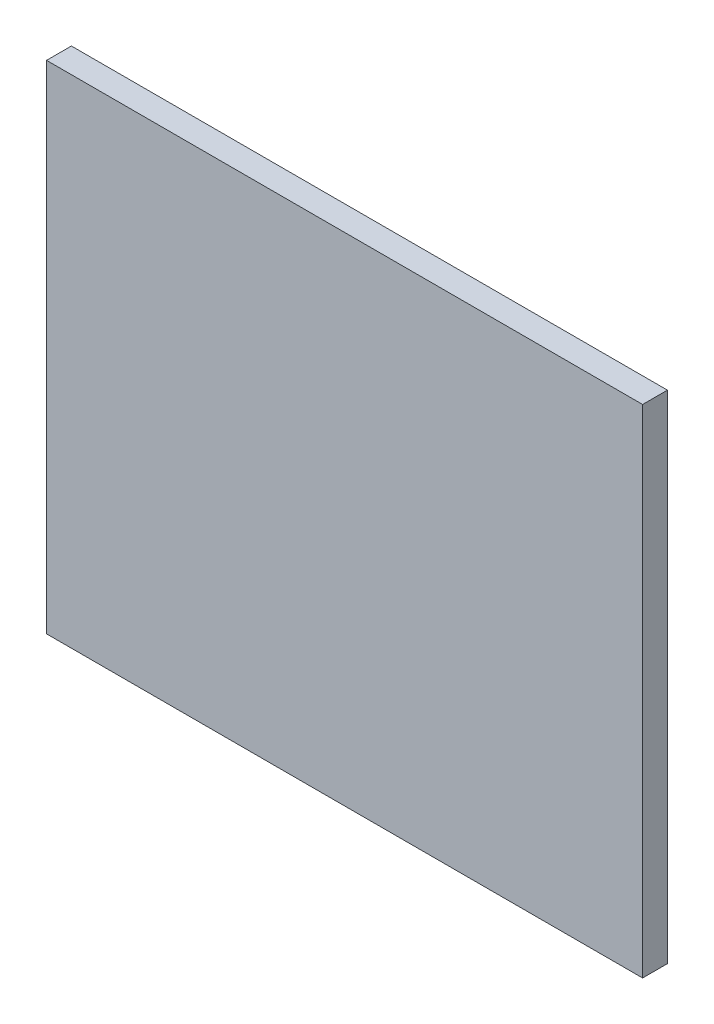
SolidWorks part; units mm, degrees
ref_plane "Plan de face" through (0, 0, 0) normal (0, 0, 1) x (1, 0, 0)
ref_plane "Plan de dessus" through (0, 0, 0) normal (0, 1, 0) x (1, 0, 0)
ref_plane "Plan de droite" through (0, 0, 0) normal (1, 0, 0) x (0, 0, -1)
sketch "Esquisse1" plane through (0, 0, 0) normal (0, 0, 1) x (1, 0, 0)
  line L0 (-14.15, 14.15) -> (-14.15, -14.15)
  line L1 (-10.15, 10.15) -> (10.15, 10.15)
  line L2 (-10.15, 10.15) -> (-10.15, -10.15)
  line L3 (-10.15, -10.15) -> (10.15, -10.15)
  line L4 (10.15, 10.15) -> (10.15, -10.15)
  line L5 (-10.15, 10.15) -> (10.15, -10.15) construction
  line L6 (-10.15, -10.15) -> (10.15, 10.15) construction
  line L7 (-14.15, -14.15) -> (14.15, -14.15)
  line L8 (14.15, 14.15) -> (14.15, -14.15)
  line L9 (-14.15, 14.15) -> (14.15, 14.15)
  line L10 (10.15, 0) -> (14.15, 0)
  line L11 (14.15, 0) -> (14.15, -2)
  line L12 (14.15, -2) -> (10.15, -2)
  line L13 (10.15, -2) -> (10.15, 0)
  line L14 (14.15, 0) -> (14.15, -2)
  line L15 (10.15, 0) -> (10.15, -2)
  point P0 (0, 0)
  dimension "D1" = 20.3
  dimension "D2" = 4
  dimension "D3" = 2
extrude "Boss.-Extru.1" add sketch "Esquisse1" along normal blind 20 contours L8 L12 L4 L3 L2 L1 L10 L9 L0 L7 | L13 L10 L11 L12 region at (0, 13.7498, 0)
extrude "Boss.-Extru.7" add sketch "Esquisse1<3>" against normal blind 20 contours L8 L12 L4 L3 L2 L1 L10 L9 L0 L7 region at (0, 13.7498, 0)
sketch "Esquisse1<3>" plane through (0, 0, 0) normal (0, 0, 1) x (1, 0, 0) same geometry as "Esquisse1"
ref_plane "Plan1" through (0, 2, 0) normal (0, -1, 0) x (-1, 0, 0)
sketch "Esquisse2" plane through (0, 2, 0) normal (0, -1, 0) x (-1, 0, 0)
  line L0 (-22.65, 0) -> (-14.15, 0) construction
  line L1 (-14.15, 20) -> (-22.65, 20)
  line L2 (-14.15, 20) -> (-14.15, -20)
  line L3 (-14.15, -20) -> (-22.65, -20) construction
  line L4 (-22.65, 20) -> (-22.65, -20)
  line L5 (-15.65, 8.4123) -> (-15.65, 11.5877)
  line L6 (-15.65, 11.5877) -> (-18.4, 13.1754)
  line L7 (-18.4, 13.1754) -> (-21.15, 11.5877)
  line L8 (-21.15, 11.5877) -> (-21.15, 8.4123)
  line L9 (-21.15, 8.4123) -> (-18.4, 6.8246)
  line L10 (-18.4, 6.8246) -> (-15.65, 8.4123)
  line L11 (-18.4, -6.8246) -> (-15.65, -8.4123) construction
  line L12 (-21.15, -8.4123) -> (-18.4, -6.8246) construction
  line L13 (-21.15, -11.5877) -> (-21.15, -8.4123) construction
  line L14 (-18.4, -13.1754) -> (-21.15, -11.5877) construction
  line L15 (-15.65, -11.5877) -> (-18.4, -13.1754) construction
  line L16 (-15.65, -8.4123) -> (-15.65, -11.5877) construction
  line L17 (-22.65, 0) -> (-14.15, -20) construction
  line L18 (-22.65, 0) -> (-14.15, 0)
  circle A0 centre (-18.4, 10) radius 2.75 construction
  circle A1 centre (-18.4, 10) radius 1.7
  circle A2 centre (-18.4, -10) radius 1.7 construction
  point P23 (-18.4, -10)
  dimension "D1" = 3.4
  dimension "D2" = 5.5
  dimension "D3" = 1.5
extrude "Boss.-Extru.2" add sketch "Esquisse2" along normal up to vertex (2 mm away) contours L1 L4 L3 L2 L10 L9 L8 L7 L6 L5 L11 L16 L15 L14 L13 L12 | L9 L10 L5 L6 L7 L8 A1 | L16 L11 L12 L13 L14 L15 A2 region at (14.3673, 2, -10) region at (17.067, 2, -7.6912) up to point (14.15, 0, -20)
extrude "Boss.-Extru.3" add sketch "Esquisse2<3>" against normal blind 3 contours L1 L4 L3 L2 L10 L9 L8 L7 L6 L5 L11 L16 L15 L14 L13 L12 region at (14.3673, 2, -10)
sketch "Esquisse2<3>" plane through (0, 2, 0) normal (0, -1, 0) x (-1, 0, 0) same geometry as "Esquisse2"
sketch "Esquisse3" plane through (0, -2, 0) normal (0, 1, 0) x (1, 0, 0)
  line L4 (22.65, 20) -> (14.15, 20)
  line L5 (14.15, 20) -> (14.15, 0)
  line L6 (14.15, 0) -> (22.65, 0)
  line L7 (22.65, 0) -> (22.65, 20)
  line L8 (22.65, 20) -> (14.15, 20)
  line L9 (14.15, 20) -> (14.15, 0)
  line L11 (22.65, 0) -> (22.65, 20)
  line L12 (14.15, 0) -> (22.65, 0)
  circle A0 centre (18.4, 10) radius 1.7 construction
  circle A1 centre (18.4, 10) radius 1.7
  dimension "D1" = 0
extrude "Boss.-Extru.4" add sketch "Esquisse3" against normal blind 2
sketch "Esquisse5" plane through (0, -4, 0) normal (0, -1, 0) x (1, 0, 0)
  line L0 (22.65, 0) -> (22.65, -20)
  line L3 (14.15, 0) -> (22.65, 0)
  line L5 (22.65, -20) -> (14.15, -20)
  line L6 (22.65, -20) -> (14.15, -20) construction
  line L7 (14.15, -20) -> (14.15, 0)
  line L8 (14.15, -20) -> (14.15, 0) construction
  circle A1 centre (18.4, -10) radius 3
  dimension "D1" = 6
extrude "Boss.-Extru.5" add sketch "Esquisse5" along normal blind 2
ref_plane "Plan3" through (0, 0, 0) normal (0, -1, 0) x (-1, 0, 0)
sketch "Esquisse6" plane through (0, 0, 0) normal (0, -1, 0) x (-1, 0, 0)
  line L0 (-14.15, -20) -> (14.15, -48.3) construction
  line L1 (14.15, -20) -> (-14.15, -20)
  line L2 (14.15, -20) -> (14.15, -48.3)
  line L3 (14.15, -48.3) -> (-14.15, -48.3)
  line L4 (-14.15, -20) -> (-14.15, -48.3)
  line L6 (-7.65, -26.5) -> (7.65, -26.5)
  line L7 (-7.65, -26.5) -> (-7.65, -41.8)
  line L8 (-7.65, -41.8) -> (7.65, -41.8)
  line L9 (7.65, -26.5) -> (7.65, -41.8)
  line L10 (-7.65, -26.5) -> (7.65, -41.8) construction
  line L11 (-7.65, -41.8) -> (7.65, -26.5) construction
  point P5 (0, -34.15)
  dimension "D1" = 15.3
extrude "Boss.-Extru.6" add sketch "Esquisse6" along normal blind 20 and the other way blind 20
sketch "Esquisse7" plane through (0, -20, 0) normal (0, -1, 0) x (1, 0, 0)
  line L0 (7.65, 34.15) -> (14.15, 34.15) construction
  line L1 (7.65, 26.5) -> (7.65, 41.8) construction
  line L2 (14.15, 20) -> (14.15, 48.3) construction
  line L3 (7.65, 34.15) -> (14.15, 34.15)
  line L4 (14.15, 34.15) -> (14.15, 36.15)
  line L5 (14.15, 36.15) -> (7.65, 36.15)
  line L6 (7.65, 36.15) -> (7.65, 34.15)
  dimension "D1" = 2
extrude "Enlèv. mat.-Extru.1" cut sketch "Esquisse7" against normal up to next
sketch "Esquisse8" plane through (0, -14.15, 0) normal (0, -1, 0) x (1, 0, 0)
  line L0 (14.15, 20) -> (14.15, -20) construction
  line L1 (14.15, 0) -> (0, 0)
  line L2 (14.15, 0) -> (14.15, 2)
  line L3 (14.15, 2) -> (0, 2)
  line L4 (0, 0) -> (0, 2)
  dimension "D1" = 2
extrude "Enlèv. mat.-Extru.2" cut sketch "Esquisse8" against normal up to next
sketch "Esquisse9" plane through (0, 0, 34.15) normal (0, 0, 1) x (1, 0, 0)
  line L0 (14.15, 20) -> (14.15, -20) construction
  line L1 (14.15, 20) -> (22.65, 20)
  line L2 (14.15, 20) -> (14.15, -20)
  line L3 (14.15, -20) -> (22.65, -20)
  line L4 (22.65, 20) -> (22.65, -20)
  line L5 (7.65, 20) -> (14.15, 20) construction
  line L6 (18.4, 20) -> (18.4, -20) construction
  line L7 (21.15, 8.4123) -> (21.15, 11.5877)
  line L8 (21.15, 11.5877) -> (18.4, 13.1754)
  line L9 (18.4, 13.1754) -> (15.65, 11.5877)
  line L10 (15.65, 11.5877) -> (15.65, 8.4123)
  line L11 (15.65, 8.4123) -> (18.4, 6.8246)
  line L12 (18.4, 6.8246) -> (21.15, 8.4123)
  line L13 (22.65, 0) -> (14.15, 0) construction
  line L14 (22.65, 20) -> (14.15, 0) construction
  line L15 (18.4, -6.8246) -> (21.15, -8.4123)
  line L16 (15.65, -8.4123) -> (18.4, -6.8246)
  line L17 (15.65, -11.5877) -> (15.65, -8.4123)
  line L18 (18.4, -13.1754) -> (15.65, -11.5877)
  line L19 (21.15, -11.5877) -> (18.4, -13.1754)
  line L20 (21.15, -8.4123) -> (21.15, -11.5877)
  circle A0 centre (18.4, 10) radius 2.75 construction
  circle A1 centre (18.4, 10) radius 1.7
  circle A2 centre (18.4, -10) radius 1.7
  line M16 (14.15, -20) -> (14.15, 20)
  dimension "D2" = 3.4
  dimension "D1" = 5.5
  dimension "D3" = 1.5
extrude "Boss.-Extru.8" add sketch "Esquisse9" against normal blind 5 contours L4 L1 L3 L12 L11 L10 L9 L8 L7 L15 L20 L19 L18 L17 L16 M16 region at (18.4, 0, 34.15)
extrude "Boss.-Extru.9" add sketch "Esquisse9<4>" against normal blind 2 contours L11 L12 L7 L8 L9 L10 A1 | L20 L15 L16 L17 L18 L19 A2 region at (19.733, 7.6912, 34.15) region at (19.733, -7.6912, 34.15)
sketch "Esquisse9<4>" plane through (0, 0, 34.15) normal (0, 0, 1) x (1, 0, 0) same geometry as "Esquisse9"
sketch "Esquisse10" plane through (0, 0, 36.15) normal (0, 0, -1) x (-1, 0, 0)
  line L4 (-22.65, 20) -> (-22.65, -20)
  line L5 (-22.65, -20) -> (-14.15, -20)
  line L6 (-14.15, -20) -> (-14.15, 20)
  line L7 (-14.15, 20) -> (-22.65, 20)
  line L8 (-22.65, 20) -> (-22.65, -20)
  line L9 (-22.65, -20) -> (-14.15, -20)
  line L10 (-14.15, -20) -> (-14.15, 20)
  line L11 (-14.15, 20) -> (-22.65, 20)
  circle A0 centre (-18.4, -10) radius 1.7 construction
  circle A1 centre (-18.4, 10) radius 1.7 construction
  circle A2 centre (-18.4, -10) radius 1.7
  circle A3 centre (-18.4, 10) radius 1.7
  dimension "D1" = 0
extrude "Boss.-Extru.10" add sketch "Esquisse10" against normal blind 2
sketch "Esquisse11" plane through (0, 0, 38.15) normal (0, 0, 1) x (1, 0, 0)
  line L4 (22.65, 20) -> (14.15, 20)
  line L5 (14.15, 20) -> (14.15, -20)
  line L6 (14.15, -20) -> (22.65, -20)
  line L7 (22.65, -20) -> (22.65, 20)
  line L8 (22.65, 20) -> (14.15, 20)
  line L9 (14.15, 20) -> (14.15, -20)
  line L10 (14.15, -20) -> (22.65, -20)
  line L11 (22.65, -20) -> (22.65, 20)
  circle A0 centre (18.4, 10) radius 3
  circle A1 centre (18.4, -10) radius 3
  dimension "D1" = 6
  dimension "D2" = 0
extrude "Boss.-Extru.11" add sketch "Esquisse11" along normal blind 2
sketch "Esquisse14" plane through (0, -20, 0) normal (0, -1, 0) x (1, 0, 0)
  line L0 (14.15, 48.3) -> (22.65, 40.15)
rib "Nervure4" sketch "Esquisse14" sketch "Esquisse14" thickness 5 extrusion direction parallel to sketch draft on no parameters "D1"=5
ref_plane "Plan4" through (0, 0, 0) normal (0, -1, 0) x (-1, 0, 0)
sketch "Esquisse16" plane through (0, -20, 0) normal (0, -1, 0) x (1, 0, 0)
  line L0 (22.65, 29.15) -> (14.15, 20)
rib "Nervure10" sketch "Esquisse16" sketch "Esquisse16" thickness 5 extrusion direction parallel to sketch draft on no parameters "D1"=5
pattern_linear "Répétition linéaire1" count 3 spacing 17.5 along (0, 1, 0) of "Nervure10", "Nervure4"
sketch "Esquisse17" plane through (0, 0, -20) normal (0, 0, -1) x (-1, 0, 0)
  line L0 (-22.65, 5) -> (-14.15, 14.15)
rib "Nervure11" sketch "Esquisse17" sketch "Esquisse17" thickness 5 extrusion direction parallel to sketch draft on no parameters "D1"=5
ref_plane "Plan5" through (0, 0, 0) normal (0, 1, 0) x (1, 0, 0)
sketch "Esquisse19" plane through (0, 0, 0) normal (0, 0, 1) x (1, 0, 0)
  line L0 (22.65, -6) -> (14.15, -14.15)
rib "Nervure17" sketch "Esquisse19" sketch "Esquisse19" thickness 5 extrusion direction parallel to sketch draft on no parameters "D1"=5
pattern_linear "Répétition linéaire2" count 2 spacing 15 along (0, 0, -1) of "Nervure17"
pattern_linear "Répétition linéaire3" count 2 spacing 15 along (0, 0, 1) of "Nervure11"
ref_plane "Plan6" through (0, 0, 2) normal (0, 0, -1) x (-1, 0, 0)
sketch "Esquisse20" plane through (0, 0, 20) normal (0, 0, -1) x (-1, 0, 0)
  line L1 (-32.3238, 24.3971) -> (45.51, 24.3971)
  line L2 (-32.3238, 24.3971) -> (-32.3238, -38.8546)
  line L3 (-32.3238, -38.8546) -> (45.51, -38.8546)
  line L4 (45.51, 24.3971) -> (45.51, -38.8546)
extrude "Enlèv. mat.-Extru.3" cut sketch "Esquisse20" against normal up to next
sketch "Esquisse21" plane through (0, 0, 20) normal (0, 0, 1) x (1, 0, 0)
  line L0 (69.5, 85) -> (-50.5, 85) construction
  line L1 (-50.5, 85) -> (69.5, 85)
  line L2 (-50.5, 85) -> (-50.5, -15)
  line L3 (-50.5, -15) -> (69.5, -15)
  line L4 (69.5, 85) -> (69.5, -15)
  line L5 (-50.5, 85) -> (69.5, -15) construction
  line L6 (-50.5, -15) -> (69.5, 85) construction
  line L7 (-50.5, -15) -> (-50.5, 85) construction
  point P0 (9.5, 35)
  point P6 (0, 0)
  point P7 (5.1439, -36.3798)
  point P8 (0.9447, -27.1144)
  point P9 (20.9835, -60.1201)
  point P10 (-50.5, 85)
  dimension "D1" = 120
  dimension "D2" = 100
extrude "Boss.-Extru.12" add sketch "Esquisse21" along normal blind 5
chamfer "Chanfrein1" distance 10 angle 45 3 edges at (14.15, 0, 20) (0, 14.15, 20) (-14.15, 0, 20)
